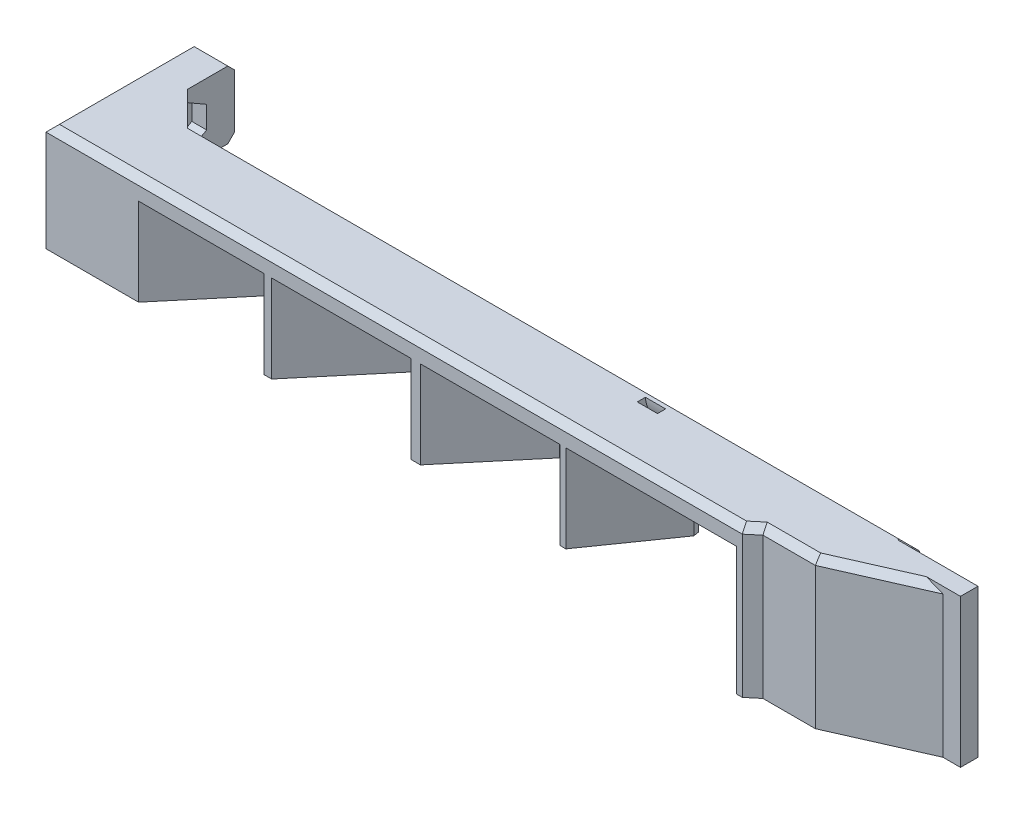
SolidWorks part; units mm, degrees
ref_plane "Front Plane" through (0, 0, 0) normal (0, 0, 1) x (1, 0, 0)
ref_plane "Top Plane" through (0, 0, 0) normal (0, 1, 0) x (1, 0, 0)
ref_plane "Right Plane" through (0, 0, 0) normal (1, 0, 0) x (0, 0, -1)
sketch "Sketch1" plane through (0, 0, 0) normal (0, 1, 0) x (1, 0, 0)
  line L1 (-16.5, 7.8333) -> (109.5, 7.8333)
  line L2 (-16.5, 7.8333) -> (-16.5, -4.1667)
  line L3 (-16.5, -4.1667) -> (109.5, -4.1667)
  line L4 (109.5, 7.8333) -> (109.5, -4.1667)
  dimension "D1" = 12
  dimension "D2" = 126
extrude "Boss-Extrude1" add sketch "Sketch1" along normal blind 16
sketch "Sketch2" plane through (0, 0, -7.8333) normal (0, 0, -1) x (-1, 0, 0)
  line L0 (-109.5, 16) -> (16.5, 16) construction
  line L1 (16.5, 0) -> (10.5, 0)
  line L2 (16.5, 0) -> (16.5, 16)
  line L3 (16.5, 16) -> (10.5, 16)
  line L4 (10.5, 0) -> (10.5, 16)
  dimension "D1" = 6
extrude "Boss-Extrude2" add sketch "Sketch2" along normal blind 10
sketch "Sketch3" plane through (-10.5, 0, 0) normal (1, 0, 0) x (0, 0, -1)
  line L0 (17.8333, 16) -> (7.8333, 16) construction
  line L1 (17.8333, 16) -> (17.8333, 0) construction
  circle A0 centre (10.8333, 11) radius 1.8
  dimension "D1" = 3.6
  dimension "D2" = 5
  dimension "D3" = 7
extrude "Cut-Extrude1" cut sketch "Sketch3" against normal blind 10
sketch "Sketch4" plane through (-10.5, 0, 0) normal (1, 0, 0) x (0, 0, -1)
  line L0 (7.8333, 16) -> (7.8333, 0) construction
  line L1 (7.9833, 12.6454) -> (7.9833, 9.3546)
  line L2 (7.9833, 9.3546) -> (10.8333, 7.7091)
  line L3 (10.8333, 7.7091) -> (13.6833, 9.3546)
  line L4 (13.6833, 9.3546) -> (13.6833, 12.6454)
  line L5 (13.6833, 12.6454) -> (10.8333, 14.2909)
  line L6 (10.8333, 14.2909) -> (7.9833, 12.6454)
  circle A0 centre (10.8333, 11) radius 2.85 construction
  dimension "D1" = 5.7
  dimension "D2" = 0
extrude "Cut-Extrude2" cut sketch "Sketch4" against normal blind 2.2
chamfer "Chamfer1" distance 3 angle 45 1 edges at (-10.5, 8, -7.8333)
sketch "Sketch6" plane through (0, 0, 0) normal (0, -1, 0) x (1, 0, 0)
  line L1 (109.5, -7.8333) -> (-7.5, -7.8333) construction
  line L2 (-16.5, 4.1667) -> (109.5, 4.1667) construction
  line L6 (67.5, -7.8333) -> (59.0975, 4.1667)
  line L7 (59.0975, 4.1667) -> (39.0975, 4.1667)
  line L8 (39.0975, 4.1667) -> (49.1667, -7.8333)
  line L9 (49.1667, -7.8333) -> (67.5, -7.8333)
  line L10 (47.0781, -7.8333) -> (37.0089, 4.1667)
  line L11 (37.0089, 4.1667) -> (17.0089, 4.1667)
  line L12 (17.0089, 4.1667) -> (27.0781, -7.8333)
  line L13 (27.0781, -7.8333) -> (47.0781, -7.8333)
  line L14 (25.2281, -7.8333) -> (15.1589, 4.1667)
  line L15 (15.1589, 4.1667) -> (-4.8411, 4.1667)
  line L16 (-4.8411, 4.1667) -> (5.2281, -7.8333)
  line L17 (5.2281, -7.8333) -> (25.2281, -7.8333)
  line L18 (7.3167, -7.8333) -> (-2.7525, 4.1667)
  line L19 (-2.7525, 4.1667) -> (-1.8197, 3.055)
  line L20 (-1.8197, 3.055) -> (-16.5, 3.055)
  line L21 (-16.5, -17.8333) -> (-16.5, 4.1667) construction
  line L22 (-16.5, 3.055) -> (-16.5, -17.8333)
  line L23 (-16.5, -17.8333) -> (-10.5, -17.8333)
  line L24 (-10.5, -17.8333) -> (-10.5, -10.8333)
  line L25 (-10.5, -10.8333) -> (-7.5, -7.8333)
  line L26 (-7.5, -7.8333) -> (7.3167, -7.8333)
  line L28 (109.5, 4.1667) -> (109.5, -7.8333) construction
  line L29 (86.8975, 4.1667) -> (101.1986, -7.8333)
  line L30 (101.1986, -7.8333) -> (109.5, -7.8333)
  line L31 (109.5, -7.8333) -> (109.5, 4.1667)
  line L32 (109.5, 4.1667) -> (109.5, 2.7667)
  line L33 (109.5, 2.7667) -> (88.566, 2.7667)
  line L34 (99.5986, -7.8333) -> (85.2975, 4.1667)
  line L35 (85.2975, 4.1667) -> (60.6975, 4.1667)
  line L36 (60.6975, 4.1667) -> (69.1, -7.8333)
  line L37 (69.1, -7.8333) -> (99.5986, -7.8333)
  line L38 (109.5, -3.0333) -> (96.345, 2.7667)
  line L39 (109.5, -5.6333) -> (98.5767, -5.6333)
  line L40 (96.9082, -4.2333) -> (106.7475, -4.2333)
  line L41 (106.7475, -4.2333) -> (106.7475, -3.3498)
  line L42 (106.7475, -3.3498) -> (96.2588, 1.2747)
  line L43 (96.2588, 1.2747) -> (93.815, -1.6378)
  line M19 (-7.5, -7.8333) -> (109.5, -7.8333)
  line M20 (109.5, -7.8333) -> (109.5, 4.1667)
  line M21 (109.5, 4.1667) -> (-16.5, 4.1667)
  dimension "D1" = 20
  dimension "D2" = 20
  dimension "D3" = 20
  dimension "D4" = 1.6
  dimension "D5" = 55
  dimension "D6" = 50
  dimension "D7" = 50
  dimension "D8" = 1.85
  dimension "D9" = 50
  dimension "D10" = 42
  dimension "D11" = 1.6
  dimension "D12" = 1.4
  dimension "D13" = 55
  dimension "D14" = 40
  dimension "D15" = 0
  dimension "D16" = 1.6
  dimension "D17" = 1.6
  dimension "D18" = 24.6
  dimension "D19" = 7.2
  dimension "D20" = 2.2
  dimension "D21" = 0
  dimension "D22" = 1.4
  dimension "D23" = 1.4
extrude "Cut-Extrude4" cut sketch "Sketch6" against normal blind 12 contours L12 L10 M21 M19 | L8 L6 M21 M19 | L18 L17 L14 M21 | L36 L34 M21 M19 | L38 L31 L33 | L42 L43 L29 L40 L41 | L39 L29 M20 M19 | L33 L31 L29 M21 region at (53.6485, 0, -1.7464) region at (78.8759, 0, -2.0474) region at (32.0435, 0, -1.8333) region at (104.664, 0, -6.6833) region at (98.6105, 0, 3.4756) region at (11.2378, 0, -1.8333) region at (99.5175, 0, -2.1942) region at (105.115, 0, 0.8333)
sketch "Sketch7" plane through (0, 0, 0) normal (0, -1, 0) x (1, 0, 0)
  line L0 (5.4667, -7.8333) -> (-2.9243, 2.1667)
  line L1 (7.3167, -7.8333) -> (-7.5, -7.8333) construction
  line L2 (-2.9243, 2.1667) -> (-16.5, 2.1667)
  line L3 (-16.5, -17.8333) -> (-16.5, 4.1667) construction
  line L4 (-16.5, 2.1667) -> (-16.5, -17.8333)
  line L5 (-16.5, -17.8333) -> (-10.5, -17.8333)
  line L6 (-10.5, -17.8333) -> (-10.5, -10.8333)
  line L7 (-10.5, -10.8333) -> (-7.5, -7.8333)
  line L8 (-7.5, -7.8333) -> (5.4667, -7.8333)
  line L10 (-16.5, 4.1667) -> (-2.7525, 4.1667) construction
  dimension "D1" = 50
  dimension "D2" = 1.85
  dimension "D3" = 2
extrude "Cut-Extrude5" cut sketch "Sketch7" against normal blind 6
sketch "Sketch8" plane through (0, 0, -7.8333) normal (0, 0, -1) x (-1, 0, 0)
  line L1 (-101.1986, 12) -> (-109.5, 12)
  line L2 (-101.1986, 12) -> (-101.1986, 16)
  line L3 (-101.1986, 16) -> (-109.5, 16)
  line L4 (-109.5, 12) -> (-109.5, 16)
extrude "Cut-Extrude6" cut sketch "Sketch8" against normal blind 2.2
sketch "Sketch9" plane through (0, 12, 0) normal (0, -1, 0) x (1, 0, 0)
  line L0 (109.5, -3.0333) -> (109.5, 4.1667)
  line L1 (109.5, 4.1667) -> (86.8975, 4.1667)
  line L2 (86.8975, 4.1667) -> (88.566, 2.7667)
  line L3 (88.566, 2.7667) -> (96.345, 2.7667)
  line L4 (96.345, 2.7667) -> (109.5, -3.0333)
extrude "Cut-Extrude7" cut sketch "Sketch9" against normal through all
sketch "Sketch10" plane through (109.5, 0, 0) normal (1, 0, 0) x (0, 0, -1)
  line L1 (5.6333, 16) -> (3.0333, 16)
  line L2 (5.6333, 16) -> (5.6333, 0)
  line L3 (5.6333, 0) -> (3.0333, 0)
  line L4 (3.0333, 16) -> (3.0333, 0)
extrude "Boss-Extrude3" add sketch "Sketch10" along normal blind 2.6
chamfer "Chamfer2" distance 2 angle 45 1 edges at (46.8493, 16, -7.8333)
chamfer "Chamfer3" distance 1 angle 45 12 edges at (-13.5, 6, -17.8333) (35.1988, 16, 4.1667) (-16.5, 16, -6.8333) (-13.5, 16, -17.8333) (15.1589, 6, 4.1667) (37.0089, 6, 4.1667) (59.0975, 6, 4.1667) (85.2975, 6, 4.1667) (69.1, 6, -7.8333) (7.3167, 6, -7.8333) (27.0781, 6, -7.8333) (49.1667, 6, -7.8333) first distance on face at (-13.5, 11, -17.8333) first distance on face at (57.5697, 16, -4.741) first distance on face at (20.1935, 6, -1.8333) first distance on face at (42.0435, 6, -1.8333) first distance on face at (63.2988, 6, -1.8333) first distance on face at (92.448, 6, -1.8333) first distance on face at (64.8988, 6, -1.8333) first distance on face at (2.2821, 6, -1.8333) first distance on face at (22.0435, 6, -1.8333) first distance on face at (44.1321, 6, -1.8333)
sketch "Sketch11" plane through (-16.5, 0, 0) normal (-1, 0, 0) x (0, 0, 1)
  line L0 (4.1667, 15) -> (-17.8333, 15) construction
  line L1 (4.1667, 15) -> (4.1667, 0) construction
  circle A0 centre (-9.8333, 6) radius 4.8
  circle A1 centre (-9.8333, 6) radius 6
  dimension "D1" = 1.2
  dimension "D2" = 12
  dimension "D3" = 9
  dimension "D4" = 14
extrude "Cut-Extrude8" cut sketch "Sketch11" against normal blind 3 from offset 12 offset against normal yes
sketch "Sketch12" plane through (0, 0, 0) normal (0, -1, 0) x (1, 0, 0)
  line L0 (86.0073, 4.1667) -> (86.0636, 3.5239)
  line L1 (86.0636, 3.5239) -> (99.5986, -7.8333)
  line L2 (99.5986, -7.8333) -> (101.1986, -7.8333)
  line L3 (101.1986, -7.8333) -> (98.5767, -5.6333)
  line L4 (98.5767, -5.6333) -> (112.1, -5.6333)
  line L5 (112.1, -5.6333) -> (112.1, -3.0333)
  line L6 (112.1, -3.0333) -> (109.5, -3.0333)
  line L7 (109.5, -3.0333) -> (96.345, 2.7667)
  line L8 (96.345, 2.7667) -> (88.566, 2.7667)
  line L9 (88.566, 2.7667) -> (86.8975, 4.1667)
  line L10 (86.8975, 4.1667) -> (86.0073, 4.1667)
  line L11 (96.2588, 1.2747) -> (93.815, -1.6378)
  line L12 (93.815, -1.6378) -> (96.9082, -4.2333)
  line L13 (96.9082, -4.2333) -> (106.7475, -4.2333)
  line L14 (106.7475, -4.2333) -> (106.7475, -3.3498)
  line L15 (106.7475, -3.3498) -> (96.2588, 1.2747)
extrude "Boss-Extrude4" add sketch "Sketch12" along normal blind 6
chamfer "Chamfer4" distance 1 angle 45 9 edges at (101.1986, 12, -6.7333) (101.1986, 16, -5.7333) (102.9225, 16, -0.1333) (92.4555, 16, 2.7667) (88.3276, 16, 2.9667) (6.5581, 12, 4.1667) (73.3524, 12, 4.1667) (49.4565, 12, 4.1667) (27.3638, 12, 4.1667)
sketch "Sketch13" plane through (112.1, 0, 0) normal (1, 0, 0) x (0, 0, -1)
  line L0 (3.0333, 16) -> (3.0333, -6) construction
  line L1 (5.6333, -6) -> (3.0333, -6) construction
  circle A0 centre (10.0333, 16.3) radius 4.8
  circle A1 centre (10.0333, 16.3) radius 6
  dimension "D1" = 1.2
  dimension "D2" = 12
  dimension "D3" = 7
  dimension "D4" = 22.3
extrude "Cut-Extrude9" cut sketch "Sketch13" against normal blind 3 from offset 46 offset against normal yes
equation "\"2.2.00mm\"=10"
equation "\"1.4.00mm\"=6"
